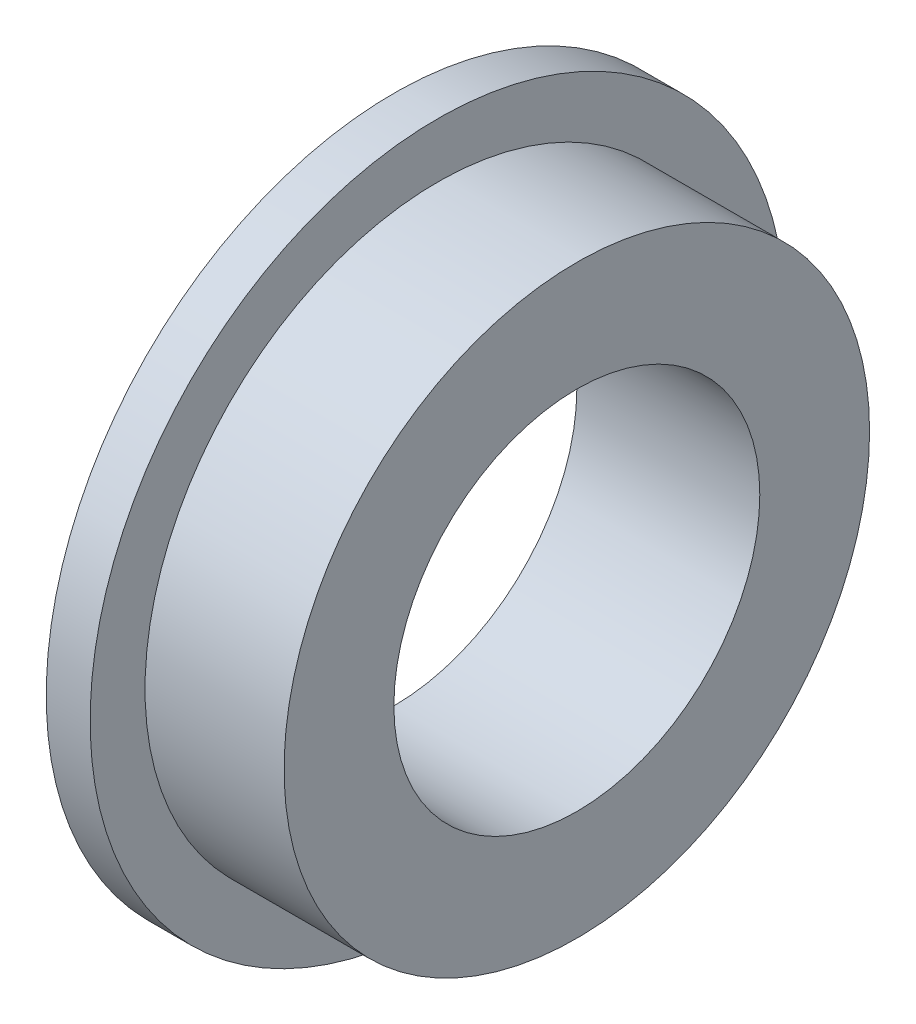
SolidWorks part; units mm, degrees
ref_plane "前视基准面" through (0, 0, 0) normal (0, 0, 1) x (1, 0, 0)
ref_plane "上视基准面" through (0, 0, 0) normal (0, 1, 0) x (1, 0, 0)
ref_plane "右视基准面" through (0, 0, 0) normal (1, 0, 0) x (0, 0, -1)
sketch "草图1" plane through (0, 0, 0) normal (1, 0, 0) x (0, 0, -1)
  circle A0 centre (0, 0) radius 4.75
  circle A1 centre (0, 0) radius 4
  circle A2 centre (0, 0) radius 2.5
  dimension "D1" = 5
  dimension "D2" = 9.5
  dimension "D3" = 8
extrude "凸台-拉伸1" add sketch "草图1" along normal blind 2.5 contours A1 A2 region at (0, 0, 3.8869)
extrude "凸台-拉伸2" add sketch "草图1<3>" along normal blind 0.6 contours A0 A1 region at (0, 0, 4.6156)
sketch "草图1<3>" plane through (0, 0, 0) normal (1, 0, 0) x (0, 0, -1) same geometry as "草图1"
